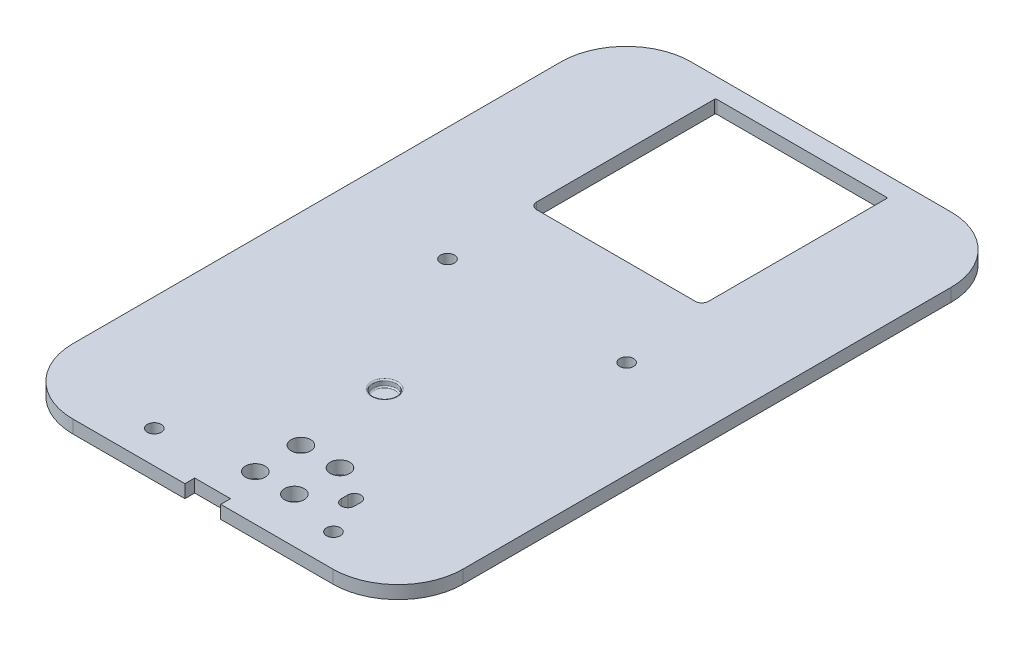
SolidWorks part; units mm, degrees
ref_plane "Front Plane" through (0, 0, 0) normal (0, 0, 1) x (1, 0, 0)
ref_plane "Top Plane" through (0, 0, 0) normal (0, 1, 0) x (1, 0, 0)
ref_plane "Right Plane" through (0, 0, 0) normal (1, 0, 0) x (0, 0, -1)
sketch "Sketch2" plane through (0, 0, 0) normal (0, 1, 0) x (1, 0, 0)
  line L0 (-25.3365, -60.2615) -> (25.3365, -60.2615)
  line L1 (-38.0365, -47.5615) -> (-38.0365, 47.5615)
  line L2 (38.0365, -47.5615) -> (38.0365, 47.5615)
  line L3 (-25.3365, 60.2615) -> (25.3365, 60.2615)
  line L4 (-38.0365, -60.2615) -> (38.0365, 60.2615) construction
  line L5 (38.0365, -60.2615) -> (-38.0365, 60.2615) construction
  arc A0 (-38.0365, 47.5615) -> (-25.3365, 60.2615) centre (-25.3365, 47.5615) cw
  arc A1 (38.0365, 47.5615) -> (25.3365, 60.2615) centre (25.3365, 47.5615) ccw
  arc A2 (25.3365, -60.2615) -> (38.0365, -47.5615) centre (25.3365, -47.5615) ccw
  arc A3 (-38.0365, -47.5615) -> (-25.3365, -60.2615) centre (-25.3365, -47.5615) ccw
  dimension "D3" = 12.7
  dimension "D4" = 12.7
  dimension "D1" = 120.523
  dimension "D2" = 76.073
extrude "top" add sketch "Sketch2" along normal blind 2.54
sketch "PCBOutline" plane through (0, 2.54, 2.54) normal (0, 1, 0) x (1, 0, 0)
  line L0 (-25.3365, -57.7215) -> (25.3365, -57.7215) construction
  line L1 (-18.9865, -55.1815) -> (22.9235, -55.1815)
  line L2 (-18.9865, -55.1815) -> (-18.9865, 9.5885)
  line L3 (-18.9865, 9.5885) -> (22.9235, 9.5885)
  line L4 (22.9235, -55.1815) -> (22.9235, 9.5885)
  line L5 (-38.0365, 50.1015) -> (-38.0365, -45.0215) construction
  dimension "D1" = 41.91
  dimension "D2" = 64.77
  dimension "D3" = 2.54
  dimension "D4" = 19.05
sketch "Sketch7" plane through (0, 2.54, 0) normal (0, 1, 0) x (1, 0, 0)
  line L1 (1.3335, -51.3715) -> (8.9535, -51.3715) construction
  line L2 (1.3335, -51.3715) -> (1.3335, -42.4815) construction
  line L3 (-18.9865, -57.7215) -> (-18.9865, 7.0485) construction
  line L4 (15.5575, -46.2915) -> (15.5575, -47.5615) construction
  line L5 (16.8275, -46.2915) -> (16.8275, -47.5615)
  line L6 (14.2875, -46.2915) -> (14.2875, -47.5615)
  line L7 (1.3335, -46.9265) -> (15.5575, -46.9265) construction
  line L8 (-18.9865, -57.7215) -> (22.9235, -57.7215) construction
  circle A0 centre (1.3335, -51.3715) radius 1.905
  circle A1 centre (8.9535, -51.3715) radius 1.905
  circle A2 centre (8.9535, -42.4815) radius 1.905
  circle A3 centre (1.3335, -42.4815) radius 1.905
  arc A4 (16.8275, -46.2915) -> (14.2875, -46.2915) centre (15.5575, -46.2915) ccw
  arc A5 (14.2875, -47.5615) -> (16.8275, -47.5615) centre (15.5575, -47.5615) ccw
  point P6 (15.5575, -46.9265)
  dimension "D7" = 3.81
  dimension "D4" = 7.62
  dimension "D5" = 8.89
  dimension "D6" = 20.32
  dimension "D8" = 14.224
  dimension "D9" = 1.27
  dimension "D10" = 2.54
  dimension "D11" = 6.35
  dimension "D2" = 2
  dimension "D3" = 2
extrude "ButtonLEDCut" cut sketch "Sketch7" against normal through all
sketch "Sketch8" plane through (0, 2.54, 0) normal (0, 1, 0) x (1, 0, 0)
  line L0 (0, 0) -> (0, 60.2615) construction
  line L1 (25.3365, 60.2615) -> (-25.3365, 60.2615) construction
  line L2 (-16.764, 20.2565) -> (-16.764, 56.4515)
  line L3 (-16.764, 20.2565) -> (16.764, 20.2565)
  line L4 (-16.764, 56.4515) -> (16.764, 56.4515)
  line L5 (16.764, 20.2565) -> (16.764, 56.4515)
  line L6 (-16.764, 20.2565) -> (16.764, 56.4515) construction
  line L7 (-16.764, 56.4515) -> (16.764, 20.2565) construction
  line L8 (-16.764, 22.1615) -> (16.764, 22.1615) construction
  point P6 (0, 38.354)
  dimension "D1" = 3.81
  dimension "D2" = 33.528
  dimension "D3" = 34.29
  dimension "D4" = 36.195
extrude "SolarCut" cut sketch "Sketch8" against normal through all
sketch "Mounting Holes" plane through (0, 2.54, 2.54) normal (0, 1, 0) x (1, 0, 0)
  line L2 (-18.9865, -55.1815) -> (-18.9865, 9.5885) construction
  line L3 (-18.9865, -55.1815) -> (22.9235, -55.1815) construction
  point P0 (-15.8115, 5.7785)
  point P2 (19.1135, 5.7785)
  point P4 (19.1135, -51.3715)
  point P6 (-15.8115, -51.3715)
  dimension "D1" = 3.175
  dimension "D2" = 3.81
  dimension "D3" = 34.925
  dimension "D4" = 57.15
hole_wizard "#6-32 Tapped Hole1" positions "Sketch12" profile "Sketch11" tap size "#6-32" standard "ANSI Inch"
sketch "Sketch12" plane through (0, 2.54, 0) normal (0, 1, 0) x (1, 0, 0)
  point P0 (-15.8115, 3.2385)
  point P3 (19.1135, 3.2385)
  point P6 (19.1135, -53.9115)
  point P9 (-15.8115, -53.9115)
sketch "Sketch11" plane through (-15.8115, 2.54, -3.2385) normal (1, 0, 0) x (0, 0, 1)
  line L0 (0, 0) -> (0, 11.9887)
  line L1 (0, 11.9887) -> (1.3525, 11.176)
  line L2 (1.3525, 11.176) -> (1.3525, 0)
  line L5 (1.3525, 0) -> (0, 0)
  line L10 (0, 11.9887) -> (-1.3526, 11.176) construction
  line L11 (0, -6.35) -> (0, 107.95) construction
  dimension "Tap Drill Dia." = 2.7051
  dimension "Tap Drill Depth" = 11.176
  dimension "Drill Angle" = 118
sketch "Sketch13" plane through (0, 0, -60.2615) normal (0, 0, -1) x (-1, 0, 0)
  line L0 (-25.3365, 0) -> (25.3365, 0) construction
  line L1 (-18.923, 0) -> (-6.477, 0)
  line L2 (-18.923, 0) -> (-18.923, 1.27)
  line L3 (-18.923, 1.27) -> (-6.477, 1.27)
  line L4 (-6.477, 0) -> (-6.477, 1.27)
  line L5 (0, 0) -> (0, 2.54) construction
  line L6 (-25.3365, 2.54) -> (25.3365, 2.54) construction
  line L7 (18.923, 0) -> (6.477, 0)
  line L8 (6.477, 0) -> (6.477, 1.27)
  line L9 (18.923, 1.27) -> (6.477, 1.27)
  line L10 (18.923, 0) -> (18.923, 1.27)
  dimension "D1" = 6.477
  dimension "D2" = 1.27
  dimension "D3" = 12.446
extrude "Body Tabs" add sketch "Sketch13" along normal blind 1.27 draft 7
sketch "Sketch14" plane through (0, 2.54, 0) normal (0, 1, 0) x (1, 0, 0)
  line L0 (0, -60.2615) -> (0, -56.9665) construction
  line L1 (-25.3365, -60.2615) -> (25.3365, -60.2615) construction
  line L3 (-3.4925, -60.2615) -> (3.4925, -60.2615)
  line L4 (-3.4925, -60.2615) -> (-3.4925, -58.3565)
  line L5 (-3.4925, -58.3565) -> (3.4925, -58.3565)
  line L6 (3.4925, -60.2615) -> (3.4925, -58.3565)
  dimension "D1" = 6.985
  dimension "D2" = 1.905
extrude "Flat Head Hole" cut sketch "Sketch14" against normal through all
sketch "Sketch15" plane through (0, 0, 60.2615) normal (0, 0, 1) x (1, 0, 0)
  line L0 (0, 0) -> (0, 2.54) construction
  line L1 (-12.7, 1.651) -> (-6.35, 1.651)
  line L2 (-12.7, 1.651) -> (-12.7, 0.889)
  line L3 (-12.7, 0.889) -> (-6.35, 0.889)
  line L4 (-6.35, 1.651) -> (-6.35, 0.889)
  line L5 (3.4925, 2.54) -> (-3.4925, 2.54) construction
  line L6 (0, 1.27) -> (-25.3365, 1.27) construction
  line L7 (-25.3365, 2.54) -> (-25.3365, 0) construction
  line L8 (-25.3365, 1.27) -> (25.3365, 1.27) construction
  line L9 (25.3365, 2.54) -> (25.3365, 0) construction
  line L10 (12.7, 1.651) -> (12.7, 0.889)
  line L11 (12.7, 0.889) -> (6.35, 0.889)
  line L12 (6.35, 1.651) -> (6.35, 0.889)
  line L13 (12.7, 1.651) -> (6.35, 1.651)
  point P16 (-6.35, 1.27)
  dimension "D1" = 0.762
  dimension "D2" = 6.35
  dimension "D3" = 6.35
extrude "Hold Grpoves" [suppressed] cut sketch "Sketch15" against normal blind 0.381
fillet "Hold Fillets" [suppressed] radius 0.381
fillet "Fillet1" radius 1.27 2 edges at (16.764, 1.27, -20.2565) (-16.764, 1.27, -20.2565)
fillet "Fillet2" radius 0.254 2 edges at (16.764, 1.27, -56.4515) (-16.764, 1.27, -56.4515)
sketch "Sketch16" plane through (0, 2.54, 0) normal (0, 1, 0) x (1, 0, 0)
  line L0 (0, 56.4515) -> (0, 20.2565) construction
  line L1 (16.51, 56.4515) -> (-16.51, 56.4515) construction
  line L2 (-15.494, 20.2565) -> (15.494, 20.2565) construction
  line L3 (0, 20.2565) -> (0, -24.8285) construction
  circle A0 centre (0, -24.8285) radius 2.286
  dimension "D2" = 4.572
  dimension "D1" = 81.28
extrude "solar solder hole" cut sketch "Sketch16" against normal blind 1.27
fillet "Fillet3" radius 0.254 2 edges at (0, 2.54, 27.1145) (0, 1.27, 27.1145)
